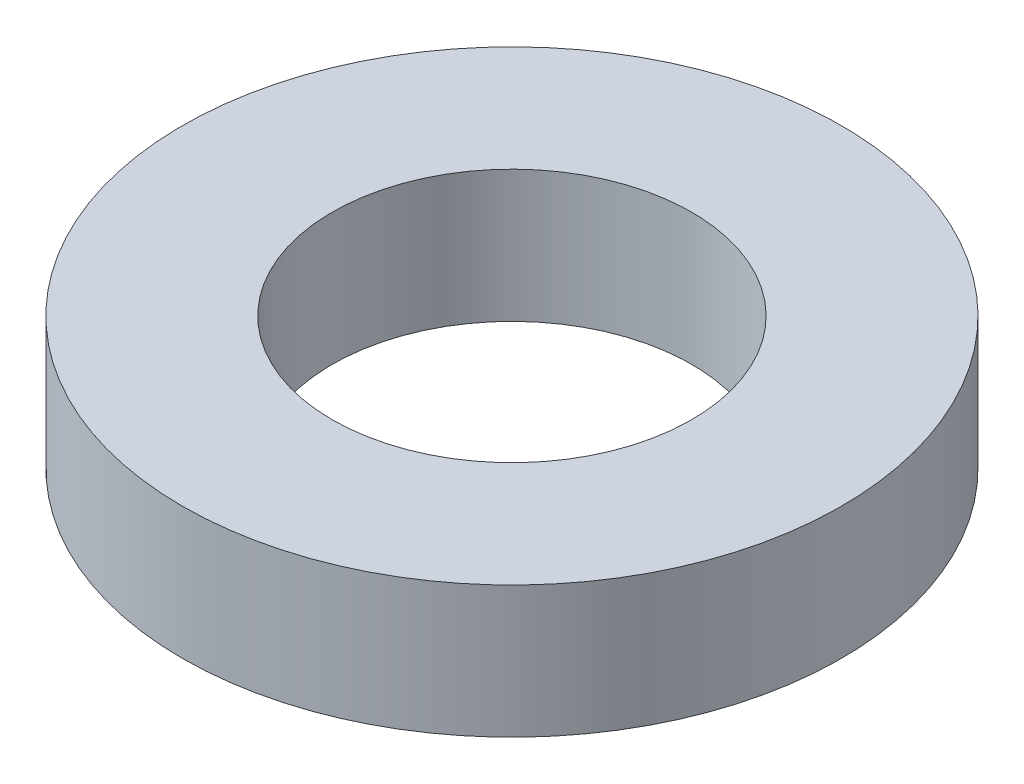
SolidWorks part; units mm, degrees
ref_plane "Front Plane" through (0, 0, 0) normal (0, 0, 1) x (1, 0, 0)
ref_plane "Top Plane" through (0, 0, 0) normal (0, 1, 0) x (1, 0, 0)
ref_plane "Right Plane" through (0, 0, 0) normal (1, 0, 0) x (0, 0, -1)
sketch "Sketch1" plane through (0, 0, 0) normal (0, 1, 0) x (1, 0, 0)
  circle A0 centre (0, 0) radius 27.5
  dimension "FLANGE_OD" = 55
extrude "Boss-Extrude1" add sketch "Sketch1" along normal blind 11
sketch "Sketch2" plane through (0, 0, 0) normal (0, 1, 0) x (1, 0, 0)
  circle A0 centre (0, 0) radius 15
  dimension "BORE_D" = 30
extrude "Cut-Extrude1" cut sketch "Sketch2" along normal through all
sketch "Sketch3" plane through (0, 11, 0) normal (0, 1, 0) x (1, 0, 0)
  circle A0 centre (0, 0) radius 11.5184 construction
  circle A1 centre (-11.5184, 0) radius 2.0024
  dimension "BOLT_D" = 4.0048
  dimension "BOLT_PCD" = 23.0368
extrude "Cut-Extrude2" cut sketch "Sketch3" against normal blind 7.3373 rebuild error yes
pattern_circular "CirPattern1" count 3 over 360 rebuild error yes
